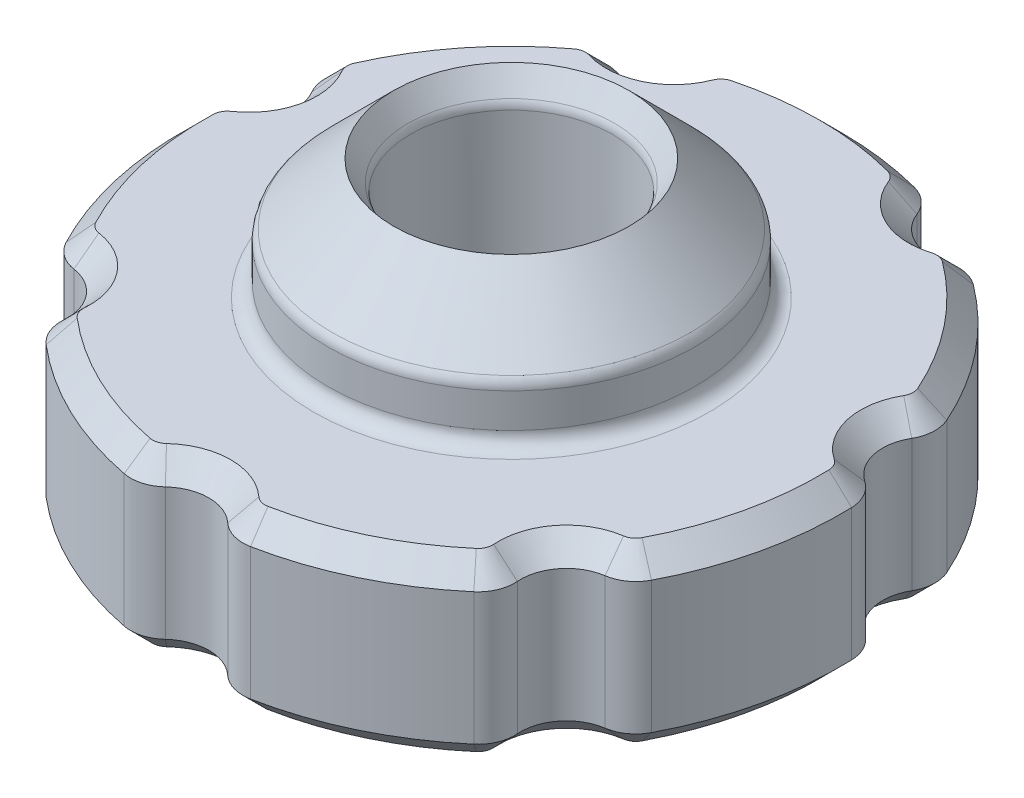
SolidWorks part; units mm, degrees
ref_plane "Front Plane" through (0, 0, 0) normal (0, 0, 1) x (1, 0, 0)
ref_plane "Top Plane" through (0, 0, 0) normal (0, 1, 0) x (1, 0, 0)
ref_plane "Right Plane" through (0, 0, 0) normal (1, 0, 0) x (0, 0, -1)
sketch "Sketch1" plane through (0, 0, 0) normal (0, 1, 0) x (1, 0, 0)
  circle A0 centre (0, 0) radius 9
  dimension "D1" = 18
extrude "Boss-Extrude1" add sketch "Sketch1" along normal blind 4.8
sketch "Sketch2" plane through (0, 4.8, 0) normal (0, 1, 0) x (1, 0, 0)
  circle A0 centre (0, 0) radius 5
  dimension "D1" = 10
extrude "Boss-Extrude2" add sketch "Sketch2" along normal blind 3.5
sketch "Sketch3" plane through (0, 8.3, 0) normal (0, 1, 0) x (1, 0, 0)
  circle A0 centre (0, 0) radius 2.75
  dimension "D1" = 5.5
extrude "Cut-Extrude1" cut sketch "Sketch3" against normal blind 6.8
chamfer "Chamfer1" distance 2 angle 45 1 edges at (0, 8.3, 5)
chamfer "Chamfer2" distance 0.6 angle 56 1 edges at (0, 8.3, 2.75) first distance on face at (0, 8.3, 3)
sketch "Sketch4" plane through (0, 0, 0) normal (0, -1, 0) x (1, 0, 0)
  line L0 (0, 0) -> (0, 9.5) construction
  circle A0 centre (0, 9.5) radius 1.25
  circle A2 centre (0, 0) radius 9.5 construction
  dimension "D1" = 2.5
  dimension "D2" = 19
extrude "Cut-Extrude2" cut sketch "Sketch4" against normal through all
pattern_circular "CirPattern1" count 7 over 360 about axis through (0, 1.5, 0) along (0, 1, 0) of "Cut-Extrude2" reverse direction yes
fillet "Fillet1" radius 1 15 edges at (1.1129, 2.4, 8.9309) (-1.1129, 2.4, 8.9309) (-6.2886, 2.4, 6.4385) (-7.6764, 2.4, 4.6982) (-8.9547, 2.4, -0.9023) (-8.4594, 2.4, -3.0724) (-4.8777, 2.4, -7.5636) (-2.8723, 2.4, -8.5294) (2.8723, 2.4, -8.5294) (4.8777, 2.4, -7.5636) (8.4594, 2.4, -3.0724) (8.9547, 2.4, -0.9023) (7.6764, 2.4, 4.6982) (6.2886, 2.4, 6.4385) (0, 1.5, 2.75)
sketch "Sketch5" plane through (0, 0, 0) normal (0, -1, 0) x (1, 0, 0)
  circle A0 centre (0, 0) radius 2
  dimension "D1" = 4
extrude "Cut-Extrude3" cut sketch "Sketch5" against normal through all
chamfer "Chamfer3" distance 0.6 angle 45 57 edges at (6.1068, 0, 6.4782) (6.4501, 0, 5.1438) (7.6746, 0, 4.5122) (8.7744, 0, 2.0027) (8.8724, 0, -0.7354) (8.0432, 0, -1.8358) (8.3128, 0, -3.187) (7.0365, 0, -5.6114) (4.9568, 0, -7.3952) (3.5795, 0, -7.433) (2.6913, 0, -8.4863) (0, 0, -9) (-2.6913, 0, -8.4863) (-3.5795, 0, -7.433) (-4.9568, 0, -7.3952) (-7.0365, 0, -5.6114) (-8.3128, 0, -3.187) (-8.0432, 0, -1.8358) (-8.8724, 0, -0.7354) (-8.7744, 0, 2.0027) (-7.6746, 0, 4.5122) (-6.4501, 0, 5.1438) (-6.1068, 0, 6.4782) (-3.905, 0, 8.1087) (-1.2573, 0, 8.8136) (0, 0, 8.25) (1.2573, 0, 8.8136) (3.905, 0, 8.1087) (8.0432, 4.8, -1.8358) (8.3128, 4.8, -3.187) (8.8724, 4.8, -0.7354) (7.0365, 4.8, -5.6114) (8.7744, 4.8, 2.0027) (4.9568, 4.8, -7.3952) (7.6746, 4.8, 4.5122) (3.5795, 4.8, -7.433) (6.4501, 4.8, 5.1438) (2.6913, 4.8, -8.4863) (6.1068, 4.8, 6.4782) (0, 4.8, -9) (3.905, 4.8, 8.1087) (-2.6913, 4.8, -8.4863) (1.2573, 4.8, 8.8136) (-3.5795, 4.8, -7.433) (0, 4.8, 8.25) (-4.9568, 4.8, -7.3952) (-1.2573, 4.8, 8.8136) (-7.0365, 4.8, -5.6114) (-3.905, 4.8, 8.1087) (-8.3128, 4.8, -3.187) (-6.1068, 4.8, 6.4782) (-8.0432, 4.8, -1.8358) (-6.4501, 4.8, 5.1438) (-8.8724, 4.8, -0.7354) (-7.6746, 4.8, 4.5122) (-8.7744, 4.8, 2.0027) (0, 0, -2)
fillet "Fillet2" radius 0.4 3 edges at (0, 4.8, 5) (0, 6.3, 5) (0, 7.4105, 2.75)
